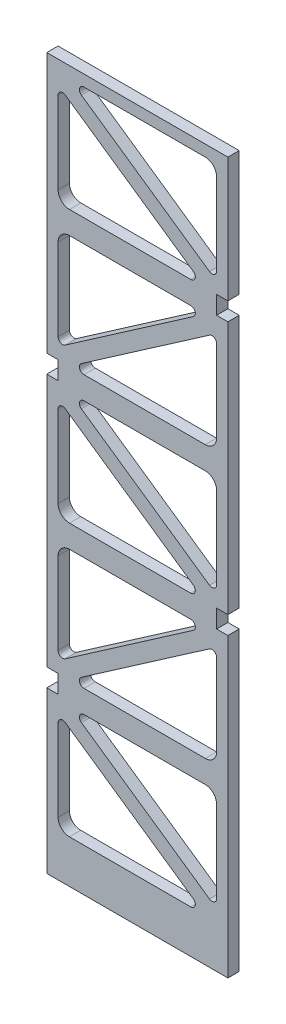
SolidWorks part; units mm, degrees
material "Balsa"
ref_plane "Front Plane" through (0, 0, 0) normal (0, 0, 1) x (1, 0, 0)
ref_plane "Top Plane" through (0, 0, 0) normal (0, 1, 0) x (1, 0, 0)
ref_plane "Right Plane" through (0, 0, 0) normal (1, 0, 0) x (0, 0, -1)
sketch "Model" plane through (0, 0, 0) normal (0, 0, 1) x (1, 0, 0)
  line L0 (88.9, 87.63) -> (20.8312, 87.63)
  line L1 (95.25, 35.3278) -> (95.25, 81.28)
  line L2 (19.3854, 83.0016) -> (91.2642, 33.2394)
  line L3 (6.35, 157.48) -> (6.35, 111.5278)
  line L4 (80.7688, 163.83) -> (12.7, 163.83)
  line L5 (10.3358, 109.4394) -> (82.2146, 159.2016)
  line L6 (88.9, 240.03) -> (20.8312, 240.03)
  line L7 (95.25, 187.7278) -> (95.25, 233.68)
  line L8 (19.3854, 235.4016) -> (91.2642, 185.6394)
  line L9 (12.7, 176.53) -> (80.7688, 176.53)
  line L10 (6.35, 228.8322) -> (6.35, 182.88)
  line L11 (82.2146, 181.1584) -> (10.3358, 230.9206)
  line L12 (91.2642, 154.7206) -> (19.3854, 104.9584)
  line L13 (95.25, 106.68) -> (95.25, 152.6322)
  line L14 (20.8312, 100.33) -> (88.9, 100.33)
  line L15 (6.35, 309.88) -> (6.35, 263.9278)
  line L16 (80.7688, 316.23) -> (12.7, 316.23)
  line L17 (10.3358, 261.8394) -> (82.2146, 311.6016)
  line L18 (88.9, 392.43) -> (20.8312, 392.43)
  line L19 (95.25, 340.1278) -> (95.25, 386.08)
  line L20 (19.3854, 387.8016) -> (91.2642, 338.0394)
  line L21 (12.7, 328.93) -> (80.7688, 328.93)
  line L22 (6.35, 381.2322) -> (6.35, 335.28)
  line L23 (82.2146, 333.5584) -> (10.3358, 383.3206)
  line L24 (12.7, 24.13) -> (80.7688, 24.13)
  line L25 (6.35, 76.4322) -> (6.35, 30.48)
  line L26 (82.2146, 28.7584) -> (10.3358, 78.5206)
  line L27 (91.2642, 307.1206) -> (19.3854, 257.3584)
  line L28 (95.25, 259.08) -> (95.25, 305.0322)
  line L29 (20.8312, 252.73) -> (88.9, 252.73)
  line L30 (0, 398.78) -> (0, 0)
  line L31 (0, 0) -> (101.6, 0)
  line L32 (101.6, 398.78) -> (101.6, 0)
  line L33 (0, 398.78) -> (101.6, 398.78)
  arc A0 (95.25, 81.28) -> (88.9, 87.63) centre (88.9, 81.28) ccw
  arc A1 (91.2642, 33.2394) -> (95.25, 35.3278) centre (92.71, 35.3278) ccw
  arc A2 (20.8312, 87.63) -> (19.3854, 83.0016) centre (20.8312, 85.09) ccw
  arc A3 (12.7, 163.83) -> (6.35, 157.48) centre (12.7, 157.48) ccw
  arc A4 (82.2146, 159.2016) -> (80.7688, 163.83) centre (80.7688, 161.29) ccw
  arc A5 (6.35, 111.5278) -> (10.3358, 109.4394) centre (8.89, 111.5278) ccw
  arc A6 (95.25, 233.68) -> (88.9, 240.03) centre (88.9, 233.68) ccw
  arc A7 (91.2642, 185.6394) -> (95.25, 187.7278) centre (92.71, 187.7278) ccw
  arc A8 (20.8312, 240.03) -> (19.3854, 235.4016) centre (20.8312, 237.49) ccw
  arc A9 (6.35, 182.88) -> (12.7, 176.53) centre (12.7, 182.88) ccw
  arc A10 (10.3358, 230.9206) -> (6.35, 228.8322) centre (8.89, 228.8322) ccw
  arc A11 (80.7688, 176.53) -> (82.2146, 181.1584) centre (80.7688, 179.07) ccw
  arc A12 (95.25, 152.6322) -> (91.2642, 154.7206) centre (92.71, 152.6322) ccw
  arc A13 (88.9, 100.33) -> (95.25, 106.68) centre (88.9, 106.68) ccw
  arc A14 (19.3854, 104.9584) -> (20.8312, 100.33) centre (20.8312, 102.87) ccw
  arc A15 (12.7, 316.23) -> (6.35, 309.88) centre (12.7, 309.88) ccw
  arc A16 (82.2146, 311.6016) -> (80.7688, 316.23) centre (80.7688, 313.69) ccw
  arc A17 (6.35, 263.9278) -> (10.3358, 261.8394) centre (8.89, 263.9278) ccw
  arc A18 (95.25, 386.08) -> (88.9, 392.43) centre (88.9, 386.08) ccw
  arc A19 (91.2642, 338.0394) -> (95.25, 340.1278) centre (92.71, 340.1278) ccw
  arc A20 (20.8312, 392.43) -> (19.3854, 387.8016) centre (20.8312, 389.89) ccw
  arc A21 (6.35, 335.28) -> (12.7, 328.93) centre (12.7, 335.28) ccw
  arc A22 (10.3358, 383.3206) -> (6.35, 381.2322) centre (8.89, 381.2322) ccw
  arc A23 (80.7688, 328.93) -> (82.2146, 333.5584) centre (80.7688, 331.47) ccw
  arc A24 (6.35, 30.48) -> (12.7, 24.13) centre (12.7, 30.48) ccw
  arc A25 (10.3358, 78.5206) -> (6.35, 76.4322) centre (8.89, 76.4322) ccw
  arc A26 (80.7688, 24.13) -> (82.2146, 28.7584) centre (80.7688, 26.67) ccw
  arc A27 (95.25, 305.0322) -> (91.2642, 307.1206) centre (92.71, 305.0322) ccw
  arc A28 (88.9, 252.73) -> (95.25, 259.08) centre (88.9, 259.08) ccw
  arc A29 (19.3854, 257.3584) -> (20.8312, 252.73) centre (20.8312, 255.27) ccw
extrude "Boss-Extrude1" add sketch "Model" along normal blind 6.35
sketch "Sketch1" plane through (0, 0, 6.35) normal (0, 0, 1) x (1, 0, 0)
  line L0 (101.6, 0) -> (101.6, 398.78) construction
  line L1 (101.6, 328.93) -> (95.25, 328.93)
  line L2 (101.6, 328.93) -> (101.6, 318.77)
  line L3 (101.6, 318.77) -> (95.25, 318.77)
  line L4 (95.25, 328.93) -> (95.25, 318.77)
  line L5 (0, 398.78) -> (0, 0) construction
  line L6 (0, 252.73) -> (6.35, 252.73)
  line L7 (0, 252.73) -> (0, 242.57)
  line L8 (0, 242.57) -> (6.35, 242.57)
  line L9 (6.35, 252.73) -> (6.35, 242.57)
  line L10 (12.7, 328.93) -> (80.7688, 328.93) construction
  line L11 (101.6, 176.53) -> (95.25, 176.53)
  line L12 (101.6, 176.53) -> (101.6, 166.37)
  line L13 (101.6, 166.37) -> (95.25, 166.37)
  line L14 (95.25, 176.53) -> (95.25, 166.37)
  line L15 (0, 100.33) -> (6.35, 100.33)
  line L16 (0, 100.33) -> (0, 90.17)
  line L17 (0, 90.17) -> (6.35, 90.17)
  line L18 (6.35, 100.33) -> (6.35, 90.17)
  line L19 (20.8312, 252.73) -> (88.9, 252.73) construction
  line L20 (12.7, 176.53) -> (80.7688, 176.53) construction
  line L21 (20.8312, 100.33) -> (88.9, 100.33) construction
  dimension "D1" = 6.35
  dimension "D2" = 10.16
  dimension "D3" = 10.16
  dimension "D4" = 6.35
  dimension "D5" = 6.35
  dimension "D6" = 10.16
  dimension "D7" = 6.35
  dimension "D8" = 10.16
extrude "Cut-Extrude1" cut sketch "Sketch1" against normal up to surface (6.35 mm away) up to face at (50.8, 199.39, 0)
equation "\"thick\"=0.25"
equation "\"D1@Boss-Extrude1\"=\"thick\""
